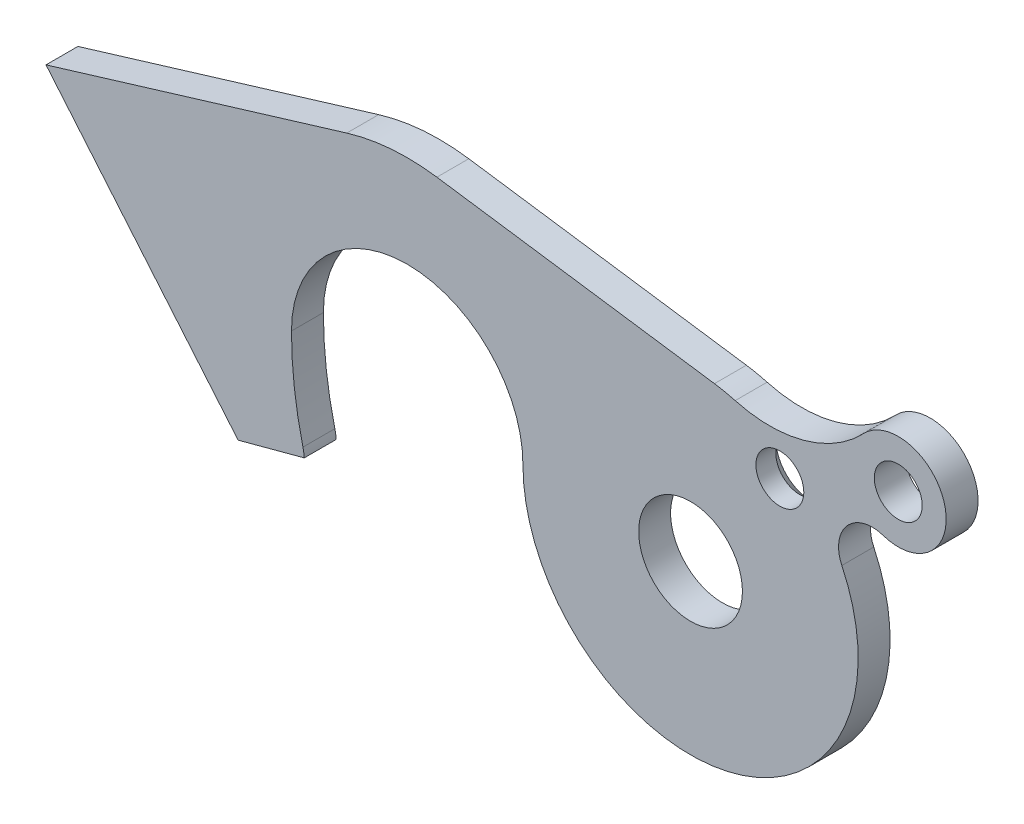
SolidWorks part; units mm, degrees
material "AISI 1020"
ref_plane "Спереди" through (0, 0, 0) normal (0, 0, 1) x (1, 0, 0)
ref_plane "Сверху" through (0, 0, 0) normal (0, 1, 0) x (1, 0, 0)
ref_plane "Справа" through (0, 0, 0) normal (1, 0, 0) x (0, 0, -1)
sketch "Эскиз1" plane through (0, 0, 0) normal (0, 0, 1) x (1, 0, 0)
  line L0 (-31.7814, 25.7981) -> (2.9961, 20.7852) construction
  line L1 (-56.6825, -15.188) -> (-48.3929, -12.9669) construction
  line L2 (-56.6825, -15.188) -> (-80.7546, 13.5) construction
  line L3 (-43.0721, 24.9406) -> (-80.7546, 13.5) construction
  line L4 (-31.7814, 25.7981) -> (2.9961, 20.7852)
  line L5 (-56.6825, -15.188) -> (-48.3929, -12.9669)
  line L6 (-56.6825, -15.188) -> (-80.7546, 13.5)
  line L7 (-43.0721, 24.9406) -> (-80.7546, 13.5)
  line L8 (15.8364, 9.3355) -> (31.8364, 9.3355) construction
  line L9 (31.8364, 9.3355) -> (0, 0) construction
  line L10 (11.1898, 14.5852) -> (26.0263, 20.5751) construction
  line L11 (26.0263, 20.5751) -> (0, 0) construction
  arc A0 (-31.7814, 25.7981) -> (-43.0721, 24.9406) centre (-35.5, 0) ccw construction
  arc A1 (-21, 0) -> (2.9961, 20.7852) centre (0, 0) ccw construction
  arc A2 (-21, 0) -> (-50, 0) centre (-35.5, 0) ccw construction
  arc A3 (-50, 0) -> (-48.5665, -11.8866) centre (0, 0) ccw construction
  arc A4 (-48.3929, -12.9669) -> (-48.5665, -11.8866) centre (-55.1586, -13.5) ccw construction
  arc A5 (-31.7814, 25.7981) -> (-43.0721, 24.9406) centre (-35.5, 0) ccw
  arc A6 (-21, 0) -> (18.9565, 9.0361) centre (0, 0) ccw
  arc A7 (-21, 0) -> (-50, 0) centre (-35.5, 0) ccw
  arc A8 (-50, 0) -> (-48.5665, -11.8866) centre (0, 0) ccw
  arc A9 (-48.3929, -12.9669) -> (-48.5665, -11.8866) centre (-55.1586, -13.5) ccw
  circle A10 centre (11.1898, 14.5852) radius 3 construction
  circle A11 centre (11.1898, 14.5852) radius 3
  circle A12 centre (0, 0) radius 6.5
  circle A13 centre (0, 0) radius 6 construction
  circle A14 centre (26.0263, 20.5751) radius 3
  arc A16 (5.5931, 20.2415) -> (21.6755, 24.7067) centre (9.9133, 35.876) ccw
  arc A17 (24.1271, 14.8836) -> (18.9565, 9.0361) centre (22.7847, 10.8609) ccw
  arc A18 (24.1271, 14.8836) -> (21.6755, 24.7067) centre (26.0263, 20.5751) ccw
  arc A19 (5.5931, 20.2415) -> (2.9961, 20.7852) centre (0, 0) ccw
  point P32 (19.6077, 13.67)
  dimension "D1" = 0.5
  dimension "D2" = 10
  dimension "D3" = 3
  dimension "D4" = 4
  dimension "D5" = 4
base flange "Базовая кромка1" sketch "Эскиз1" thickness 4 reverse thickness direction yes parameters "D1"=3
chamfer "Фаска1" [suppressed] distance 1.5 angle 45
chamfer "Фаска2" distance 1.5 angle 45 1 edges at (14.1898, 14.5852, 0)
sketch "Сгиб-Линии1" [suppressed] plane through (0, 0, 0) normal (0, 1, 0) x (1, 0, 0)
sketch "Граничная рамка1" [suppressed] plane through (0, 0, 0) normal (0, 1, 0) x (1, 0, 0)
sheet metal parameters "Листовой металл3" thickness 4 parameters "D1"=3
flat pattern "Развертка3" [suppressed]
sketch "Сгиб-Линии2" plane through (0, 0, 0) normal (0, 1, 0) x (1, 0, 0)
sketch3d "Граничная рамка2" [suppressed]
  line L0 (44.9633, -21.6671, 0) -> (-67.8687, -20.7326, 0) construction
  line L1 (45.3555, 25.69, 0) -> (-67.4764, 26.6245, 0) construction
  line L2 (44.9633, -21.6671, 0) -> (45.3555, 25.69, 0) construction
  line L3 (-67.8687, -20.7326, 0) -> (-67.4764, 26.6245, 0) construction
